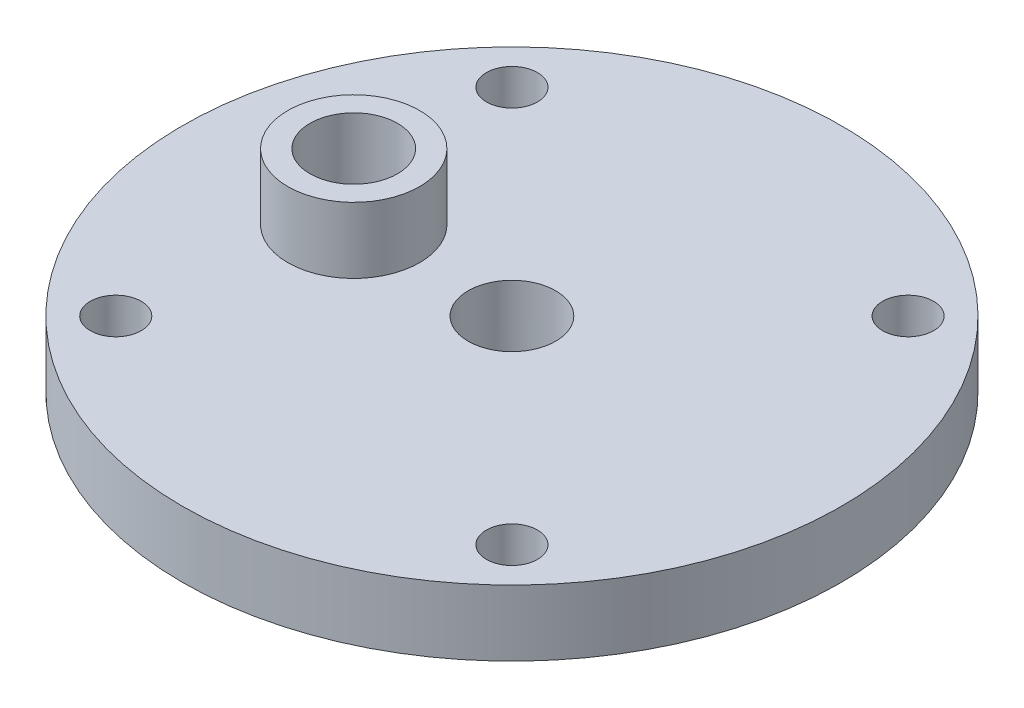
SolidWorks part; units mm, degrees
material "1023 Carbon Steel Sheet (SS)"
ref_plane "Front Plane" through (0, 0, 0) normal (0, 0, 1) x (1, 0, 0)
ref_plane "Top Plane" through (0, 0, 0) normal (0, 1, 0) x (1, 0, 0)
ref_plane "Right Plane" through (0, 0, 0) normal (1, 0, 0) x (0, 0, -1)
ref_axis "Axis1" through (0, 10.0012, 0) along (0, -1, 0)
ref_plane "Plane1" through (0, 0, 0) normal (0, 0, 1) x (0, -1, 0)
sketch "Sketch1" plane through (0, 0, 0) normal (0, 0, 1) x (1, 0, 0)
  line L0 (0, 0) -> (-15.875, 0)
  line L1 (-15.875, 0) -> (-15.875, 3.175)
  line L2 (-15.875, 3.175) -> (-12.7, 3.175)
  line L4 (-15.875, 7.9375) -> (-31.75, 7.9375)
  line L5 (-31.75, 7.9375) -> (-31.75, 14.2875)
  line L6 (-31.75, 14.2875) -> (0, 14.2875)
  line L7 (0, 14.2875) -> (0, 0)
  line L8 (-15.875, 7.9375) -> (-15.875, 6.35)
  line L9 (-15.875, 6.35) -> (-12.7, 6.35)
  line L10 (-12.7, 6.35) -> (-12.7, 3.175)
  point P10 (-15.875, 1.5875)
  dimension "D1" = 15.875
  dimension "D2" = 3.175
  dimension "D3" = 3.175
  dimension "D4" = 6.35
  dimension "D5" = 31.75
  dimension "D6" = 3.175
  dimension "D7" = 1.5875
revolve "Revolve1" add sketch "Sketch1" angle 360 about L7
hole_wizard "Pipe Tap Drill for 1/8 Tap1" positions "3DSketch1" profile "Sketch2" hole size "1/8" standard "ANSI Inch"
sketch3d "3DSketch1"
  circle A0 centre (0, 14.2875, 0) radius 31.75 construction
  point P0 (0, 14.2875, 0)
  point P5 (0, 46.0375, 0)
sketch "Sketch2" plane through (0, 14.2875, 0) normal (1, 0, 0) x (0, 0, 1)
  line L0 (0, 0) -> (0, 27.9335)
  line L1 (0, 27.9335) -> (4.2164, 25.4)
  line L2 (4.2164, 25.4) -> (4.2164, 0)
  line L5 (4.2164, 0) -> (0, 0)
  line L10 (0, 27.9335) -> (-4.2164, 25.4) construction
  line L11 (0, -6.35) -> (0, 107.95) construction
  dimension "Hole Dia." = 8.4328
  dimension "Hole Depth" = 25.4
  dimension "Drill Angle" = 118
sketch "Sketch3" plane through (0, 0, 0) normal (0, 0, -1) x (-1, 0, 0)
  line L0 (-11.5679, 5.2179) -> (0, -6.35)
  line L1 (-11.3883, 5.3975) -> (-11.7475, 5.0383)
  line L2 (-11.7475, 5.0383) -> (-5.08, -1.6292)
  line L3 (-5.08, -1.6292) -> (-4.7208, -1.27)
  line L4 (-4.7208, -1.27) -> (-11.3883, 5.3975)
  line L5 (0, 0) -> (0, -6.35) construction
  line L6 (-15.875, 0) -> (15.875, 0) construction
  line L7 (-31.75, 7.9375) -> (31.75, 7.9375) construction
  point P4 (-11.5679, 5.2179)
  dimension "D1" = 45
  dimension "D2" = 0.508
  dimension "D3" = 6.35
  dimension "D4" = 1.27
  dimension "D5" = 2.54
revolve "Cut-Revolve2" cut sketch "Sketch3" angle 360 about L0 region at (8.1443, 1.9739, 0)
pattern_circular "CirPattern1" count 4 over 360 about axis through (0, 14.2875, 0) along (0, 1, 0) of "Cut-Revolve2" reverse direction yes
sketch "Sketch5" plane through (0, 14.2875, 0) normal (0, 1, 0) x (1, 0, 0)
  line L0 (-15.24, 0) -> (0, 0) construction
  circle A0 centre (-15.24, 0) radius 6.35
  dimension "D2" = 12.7
  dimension "D1" = 15.24
extrude "Boss-Extrude1" add sketch "Sketch5" along normal blind 6.35
hole_wizard "Pipe Tap Drill for 1/8 Tap2" positions "3DSketch2" profile "Sketch4" hole size "1/8" standard "ANSI Inch"
sketch3d "3DSketch2"
  line L2 (-15.24, 20.6375, 0) -> (0, 20.6375, 0) construction
  circle A0 centre (-15.24, 20.6375, 0) radius 6.35 construction
  point P0 (-15.24, 20.6375, 0)
  point P20 (-15.24, 26.9875, 0)
sketch "Sketch4" plane through (-15.24, 20.6375, 0) normal (1, 0, 0) x (0, 0, 1)
  line L0 (0, 0) -> (0, 8.8835)
  line L1 (0, 8.8835) -> (4.2164, 6.35)
  line L2 (4.2164, 6.35) -> (4.2164, 0)
  line L5 (4.2164, 0) -> (0, 0)
  line L10 (0, 8.8835) -> (-4.2164, 6.35) construction
  line L11 (0, -6.35) -> (0, 107.95) construction
  dimension "Hole Dia." = 8.4328
  dimension "Hole Depth" = 6.35
  dimension "Drill Angle" = 118
hole_wizard "1/8 (0.125) Diameter Hole4" positions "3DSketch3" profile "Sketch7" hole size "1/8" standard "ANSI Inch" end condition up to next
sketch3d "3DSketch3"
  circle A0 centre (-15.24, 20.6375, 0) radius 4.2164 construction
  point P0 (-15.24, 20.6375, 0)
  point P5 (-15.24, 24.8539, 0)
sketch "Sketch7" plane through (-15.24, 20.6375, 0) normal (1, 0, 0) x (0, 0, 1)
  line L0 (0, 0) -> (0, 14.2875)
  line L1 (0, 14.2875) -> (1.5875, 14.2875)
  line L2 (1.5875, 14.2875) -> (1.5875, 0)
  line L5 (1.5875, 0) -> (0, 0)
  line L11 (0, -6.35) -> (0, 107.95) construction
  dimension "Thru Hole Dia." = 3.175
  dimension "Thru Hole Depth" = 14.2875
hole_wizard "#10 (0.1935) Diameter Hole1" positions "3DSketch4" profile "Sketch8" hole size "#10" standard "ANSI Inch" end condition up to next
sketch3d "3DSketch4"
  line L0 (19.083, 14.2875, -19.083) -> (0, 14.2875, 0) construction
  line L1 (0, 14.2875, 0) -> (31.75, 14.2875, 0) construction
  line L3 (19.083, 14.2875, -19.083) -> (22.4506, 14.2875, -22.4506) construction
  circle A0 centre (0, 14.2875, 0) radius 31.75 construction
  point P0 (19.083, 14.2875, -19.083)
  point P8 (0, 46.0375, 0)
  dimension "D1" = 45
  dimension "D2" = 4.7625
sketch "Sketch8" plane through (19.083, 14.2875, -19.083) normal (1, 0, 0) x (0, 0, 1)
  line L0 (0, 0) -> (0, 6.35)
  line L1 (0, 6.35) -> (2.4574, 6.35)
  line L2 (2.4574, 6.35) -> (2.4574, 0)
  line L5 (2.4574, 0) -> (0, 0)
  line L11 (0, -6.35) -> (0, 107.95) construction
  dimension "Thru Hole Dia." = 4.9149
  dimension "Thru Hole Depth" = 6.35
pattern_circular "CirPattern2" count 4 over 360 about axis through (0, 14.2875, 0) along (0, 1, 0) of "#10 (0.1935) Diameter Hole1"
